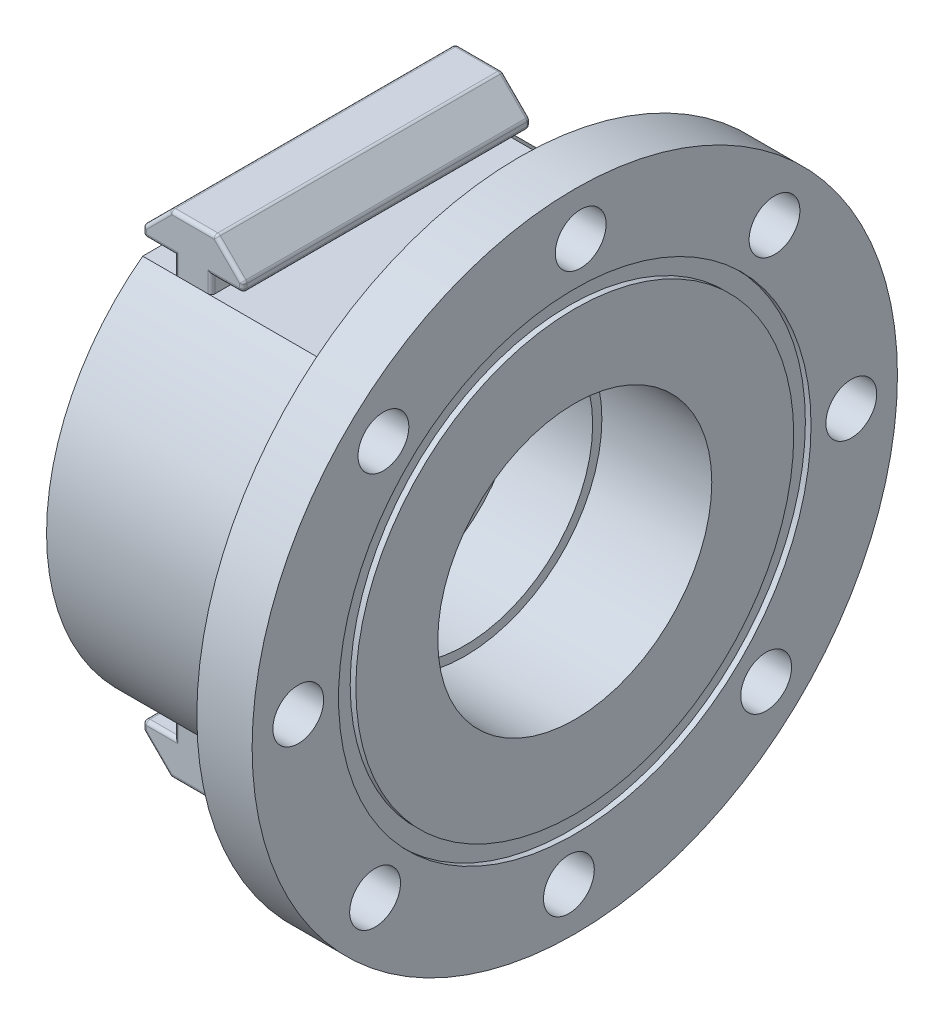
SolidWorks part; units mm, degrees
ref_plane "Front Plane" through (0, 0, 0) normal (0, 0, 1) x (1, 0, 0)
ref_plane "Top Plane" through (0, 0, 0) normal (0, 1, 0) x (1, 0, 0)
ref_plane "Right Plane" through (0, 0, 0) normal (1, 0, 0) x (0, 0, -1)
sketch "Main sketch" plane through (0, 0, 0) normal (0, 0, 1) x (1, 0, 0)
  line L0 (0, 9) -> (0, 19.995)
  line L1 (0, 19.995) -> (-8, 19.995)
  line L2 (-8, 19.995) -> (-8, 33.02)
  line L3 (-8, 33.02) -> (24.13, 33.02)
  line L4 (24.13, 33.02) -> (24.13, 44.45)
  line L5 (24.13, 44.45) -> (31.75, 44.45)
  line L6 (31.75, 44.45) -> (31.75, 32.5438)
  line L7 (31.75, 32.5438) -> (30.9721, 32.5438)
  line L8 (30.9721, 32.5438) -> (30.9721, 30.1625)
  line L9 (30.9721, 30.1625) -> (31.75, 30.1625)
  line L10 (31.75, 30.1625) -> (31.75, 18.8722)
  line L11 (31.75, 18.8722) -> (16.6116, 18.8722)
  line L12 (16.6116, 18.8722) -> (16.6116, 17.6022)
  line L13 (16.6116, 17.6022) -> (6.35, 17.6022)
  line L14 (6.35, 17.6022) -> (6.35, 9)
  line L15 (6.35, 9) -> (0, 9)
  line L16 (0, 0) -> (0, 9) construction
  dimension "D1" = 9
  dimension "D2" = 19.995
  dimension "D3" = 25.4
  dimension "D4" = 17.6022
  dimension "D5" = 8
  dimension "D6" = 44.45
  dimension "D7" = 18.8722
  dimension "D8" = 32.5437
  dimension "D11" = 6.35
  dimension "D12" = 10.2616
  dimension "D13" = 33.02
  dimension "D14" = 7.62
  dimension "D9" = 30.1625
  dimension "D10" = 0.7779
ref_axis "Axis1" through (71.9501, 0, 0) along (-1, 0, 0)
revolve "Revolve1" add sketch "Main sketch" angle 360 about axis through (71.9501, 0, 0) along (-1, 0, 0)
sketch "Sketch2" plane through (31.75, 0, 0) normal (1, 0, 0) x (0, 0, -1)
  circle A0 centre (0, 0) radius 38.1 construction
  point P0 (0, 0)
  point P3 (-38.0913, 0.8131)
  point P4 (-27.5096, -26.3597)
  point P7 (-0.8131, -38.0913)
  point P8 (26.3597, -27.5096)
  point P9 (38.0913, -0.8131)
  point P10 (27.5096, 26.3597)
  point P11 (0.8131, 38.0913)
  point P12 (-26.3597, 27.5096)
  point P13 (0, 0)
  point P16 (0, 0)
  dimension "D2" = 76.2
  dimension "D1" = 8
hole_wizard "M6 Clearance Hole1" positions "Sketch2" profile "Sketch3" hole size "M6" standard "ISO" end condition through all
sketch "Sketch3" plane through (31.75, 0, 0) normal (0, 1, 0) x (0, 0, -1)
  line L0 (0, 0) -> (0, 39.75)
  line L1 (0, 39.75) -> (3.5, 39.75)
  line L2 (3.5, 39.75) -> (3.5, 0)
  line L5 (3.5, 0) -> (0, 0)
  line L11 (0, -6.35) -> (0, 107.95) construction
  dimension "Thru Hole Dia." = 7
  dimension "Thru Hole Depth" = 39.75
ref_plane "Plane1" through (0, 0, 33.02) normal (0, 0, 1) x (1, 0, 0)
ref_plane "Plane2" through (0, 33.02, 0) normal (0, 1, 0) x (1, 0, 0)
ref_plane "Plane3" through (0, 0, -33.02) normal (0, 0, -1) x (-1, 0, 0)
sketch "Sketch4" plane through (0, 33.02, 0) normal (0, 1, 0) x (1, 0, 0)
  line L0 (-8, -33.02) -> (24.13, -33.02) construction
  line L1 (24.13, 33.02) -> (24.13, -33.02) construction
  line L2 (24.13, 33.02) -> (-8, 33.02) construction
  line L3 (-8, 33.02) -> (-8, -33.02) construction
  line L4 (-8, -33.02) -> (24.13, -33.02)
  line L5 (24.13, 33.02) -> (24.13, -33.02)
  line L6 (24.13, 33.02) -> (-8, 33.02)
  line L7 (-8, 33.02) -> (-8, -33.02)
extrude "Cut-Extrude1" cut sketch "Sketch4" against normal blind 6.5786
ref_plane "Plane4" through (0, 0, -19.7781) normal (0, 0, 1) x (1, 0, 0)
ref_plane "Plane5" through (0, 0, 19.7781) normal (0, 0, -1) x (-1, 0, 0)
sketch "Sketch5" plane through (0, 0, 19.7781) normal (0, 0, -1) x (-1, 0, 0)
  line L0 (8, 26.4414) -> (-24.13, 26.4414) construction
  line L1 (8, 26.4414) -> (-24.13, 26.4414)
  line L2 (-1.4742, 26.4414) -> (-1.4742, 28.8036)
  line L3 (-1.4742, 28.8036) -> (-5.8684, 28.8036)
  line L4 (-5.8684, 28.8036) -> (-5.8684, 30.0736)
  line L5 (-5.8684, 30.0736) -> (-2.0584, 33.8836)
  line L6 (-2.0584, 33.8836) -> (4.19, 33.8836)
  line L7 (1.0658, 33.8836) -> (1.0658, 26.4414) construction
  line L8 (3.6058, 26.4414) -> (-1.4742, 26.4414)
  line L9 (3.6058, 26.4414) -> (3.6058, 28.8036)
  line L10 (3.6058, 28.8036) -> (8, 28.8036)
  line L11 (8, 28.8036) -> (8, 30.0736)
  line L12 (8, 30.0736) -> (4.19, 33.8836)
  line L13 (8, -33.02) -> (8, 26.4414) construction
  dimension "D1" = 2.54
  dimension "D2" = 2.3622
  dimension "D3" = 135
  dimension "D4" = 5.08
  dimension "D5" = 6.9342
  dimension "D6" = 1.27
extrude "Boss-Extrude1" add sketch "Sketch5" along normal up to surface (39.5562 mm away) contours L7 L6 L5 L4 L3 L2 L8 | L6 L7 L1 L9 L10 L11 L12 region at (-3.6753, 30.4149, 19.7781) region at (1.5437, 30.4149, 19.7781) up to plane "Plane4"
fillet "Fillet1" radius 0.508 24 edges at (-1.0658, 33.8836, -19.7781) (1.4742, 27.6225, 19.7781) (5.8684, 29.4386, 19.7781) (3.6713, 28.8036, 19.7781) (3.9634, 31.9786, 19.7781) (-1.0658, 33.8836, 19.7781) (-5.8029, 28.8036, 19.7781) (-3.6058, 27.6225, 19.7781) (1.4742, 27.6225, -19.7781) (-3.6058, 27.6225, -19.7781) (-5.8029, 28.8036, -19.7781) (-6.095, 31.9786, -19.7781) (-4.19, 33.8836, 0) (-6.095, 31.9786, 19.7781) (-8, 29.4386, 19.7781) (-8, 30.0736, 0) (-8, 28.8036, 0) (-8, 29.4386, -19.7781) (3.9634, 31.9786, -19.7781) (5.8684, 29.4386, -19.7781) (3.6713, 28.8036, -19.7781) (2.0584, 33.8836, 0) (5.8684, 30.0736, 0) (5.8684, 28.8036, 0)
mirror "Mirror1" about plane through (0, 0, 0) normal (0, 1, 0) of "Fillet1", "Boss-Extrude1", "Cut-Extrude1"
equation "\"Shaft_OD\"= 17mm"
equation "\"O_Ring_ID\"= 2.375in"
equation "\"O_Ring_CS\"= 1 / 16in'cross section"
equation "\"Bearing_OD\"= 39.99mm"
equation "\"Bearing_Depth\"= 8mm"
equation "\"Stationary_Face_Seal_OD\"= 1.386in"
equation "\"Flange_Dia\"= 3.5in"
equation "\"Screw_Dia\"= 6mm"
equation "\"Screws\"= 8"
equation "\"Seal_Space\"= 1in"
equation "\"D1@Main sketch\"=\"Shaft_OD\" / 2 + .5mm"
equation "\"D2@Main sketch\" = \"Bearing_OD\" / 2"
equation "\"D3@Main sketch\" = \"Seal_Space\""
equation "\"D4@Main sketch\" = \"Stationary_Face_Seal_OD\" / 2"
equation "\"D5@Main sketch\" = \"Bearing_Depth\""
equation "\"D6@Main sketch\" = \"Flange_Dia\" / 2"
equation "\"Seal_Area_Dia\"= 37mm"
equation "\"D7@Main sketch\" =  ( \"Stationary_Face_Seal_OD\" / 2 )  + .05in"
equation "\"D8@Main sketch\"=\"O_Ring_ID\" / 2 + \"O_Ring_CS\" * 1.5"
equation "\"Face_Seal_Height\"=0.404"
equation "\"D12@Main sketch\" = \"Face_Seal_Height\""
equation "\"Housing_OR\"= 1.3"
equation "\"D13@Main sketch\"=\"Housing_OR\""
equation "\"D10@Main sketch\"=\"O_Ring_CS\"*.49"
equation "\"D9@Main sketch\"=\"O_Ring_ID\"/2"
equation "\"D2@Sketch2\"=\"Flange_Dia\"-.50"
